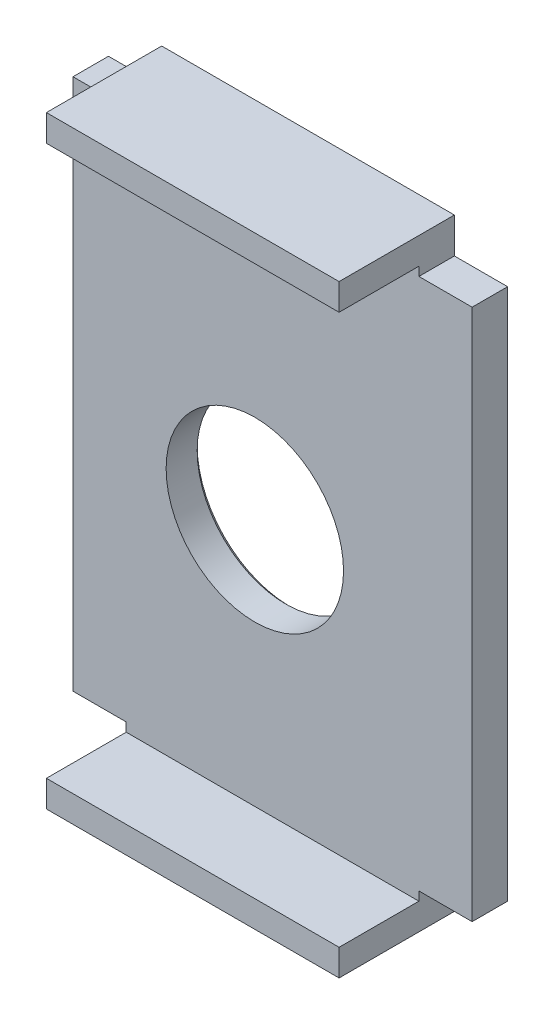
SolidWorks part; units mm, degrees
ref_plane "Front Plane" through (0, 0, 0) normal (0, 0, 1) x (1, 0, 0)
ref_plane "Top Plane" through (0, 0, 0) normal (0, 1, 0) x (1, 0, 0)
ref_plane "Right Plane" through (0, 0, 0) normal (1, 0, 0) x (0, 0, -1)
sketch "Sketch1" plane through (0, 0, 0) normal (0, 0, 1) x (1, 0, 0)
  line L5 (-22.5, -30) -> (22.5, -30)
  line L6 (-22.5, -30) -> (-22.5, 30)
  line L7 (-22.5, 30) -> (22.5, 30)
  line L8 (22.5, -30) -> (22.5, 30)
  line L9 (-22.5, -30) -> (22.5, 30) construction
  line L10 (-22.5, 30) -> (22.5, -30) construction
  circle A2 centre (-2, -3) radius 10
  point P0 (0, 0)
  dimension "D3" = 20
  dimension "D4" = 20.5
  dimension "D1" = 60
  dimension "D2" = 45
  dimension "D5" = 3
extrude "Boss-Extrude1" add sketch "Sketch1" along normal mid plane 4
sketch "Sketch3" plane through (0, 0, -2) normal (0, 0, -1) x (-1, 0, 0)
  line L0 (-22.5, 30) -> (22.5, 30) construction
  line L1 (-16.5, 30) -> (16.5, 30)
  line L2 (-16.5, 30) -> (-16.5, 34)
  line L3 (-16.5, 34) -> (16.5, 34)
  line L4 (16.5, 30) -> (16.5, 34)
  line L5 (-22.5, -30) -> (-22.5, 30) construction
  line L6 (22.5, 30) -> (22.5, -30) construction
  line L7 (22.5, -30) -> (-22.5, -30) construction
  line L8 (-16.5, -30) -> (16.5, -30)
  line L9 (-16.5, -30) -> (-16.5, -34)
  line L10 (-16.5, -34) -> (16.5, -34)
  line L11 (16.5, -30) -> (16.5, -34)
  dimension "D1" = 6
  dimension "D2" = 6
  dimension "D3" = 4
extrude "Boss-Extrude3" add sketch "Sketch3" against normal blind 13
chamfer "Chamfer1" distance 0.5 angle 45 1 edges at (8, -3, -2)
sketch "Sketch4" plane through (0, 0, 11) normal (0, 0, 1) x (1, 0, 0)
  line L0 (16.5, 34) -> (16.5, 30) construction
  line L1 (-16.5, 30) -> (16.5, 30)
  line L2 (-16.5, 30) -> (-16.5, 31)
  line L3 (-16.5, 31) -> (16.5, 31)
  line L4 (16.5, 30) -> (16.5, 31)
  line L5 (-16.5, -34) -> (-16.5, -30) construction
  line L6 (16.5, -30) -> (-16.5, -30)
  line L7 (16.5, -30) -> (16.5, -31)
  line L8 (16.5, -31) -> (-16.5, -31)
  line L9 (-16.5, -30) -> (-16.5, -31)
  dimension "D1" = 1
extrude "Cut-Extrude1" cut sketch "Sketch4" against normal up to vertex (9 mm away) up to point (16.5, -30, 2)
equation "\"padding\"=6"
equation "\"wall_thick_ness\"=4"
equation "\"D1@Sketch3\"=\"padding\""
equation "\"D2@Sketch3\"=\"padding\""
equation "\"D3@Sketch3\"=\"wall_thick_ness\""
equation "\"D1@Boss-Extrude1\"=\"wall_thick_ness\""
